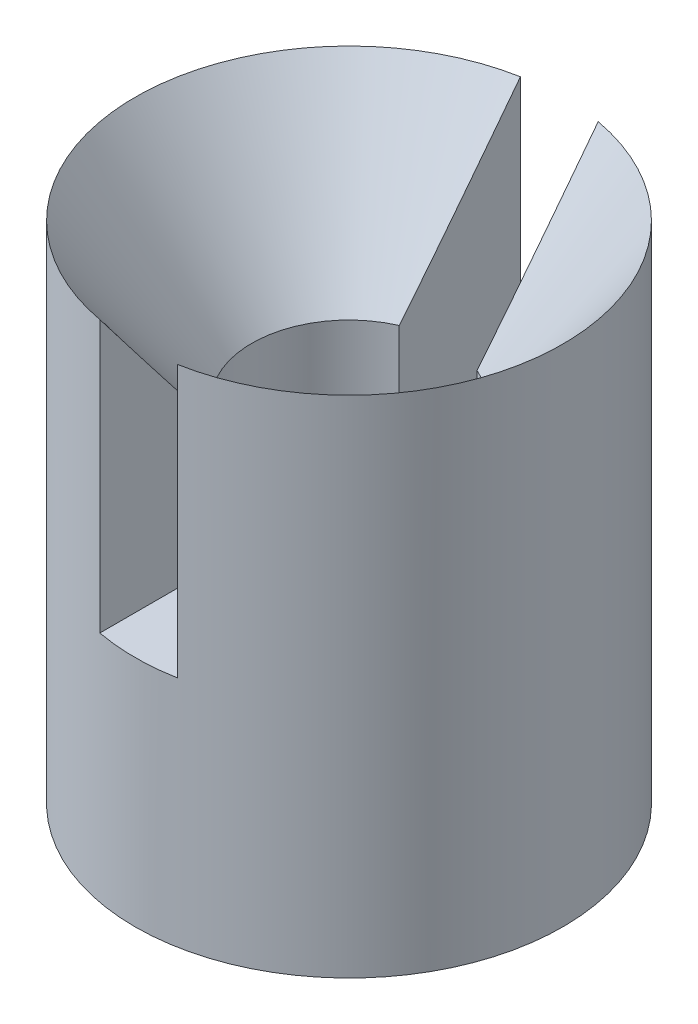
SolidWorks part; units mm, degrees
material "PBT General Purpose"
ref_plane "Front" through (0, 0, 0) normal (0, 0, 1) x (1, 0, 0)
ref_plane "Top" through (0, 0, 0) normal (0, 1, 0) x (1, 0, 0)
ref_plane "Right" through (0, 0, 0) normal (1, 0, 0) x (0, 0, -1)
sketch "Sketch1" plane through (0, 0, 0) normal (0, 1, 0) x (1, 0, 0)
  circle A0 centre (0, 0) radius 5.5
  dimension "D1" = 11
extrude "Boss-Extrude1" add sketch "Sketch1" along normal blind 13
sketch "Sketch2" plane through (0, 0, 0) normal (0, -1, 0) x (1, 0, 0)
  circle A0 centre (0, 0) radius 2.5
extrude "Cut-Extrude1" cut sketch "Sketch2" against normal through all
chamfer "Chamfer1" distance 4 angle 37 1 edges at (0, 13, -2.5) first distance on face at (0, 13, -2.5)
ref_plane "Plane1" through (0, 13, 0) normal (0, 1, 0) x (1, 0, 0)
sketch "Sketch4" plane through (0, 13, 0) normal (0, 1, 0) x (1, 0, 0)
  line L1 (-1, -6) -> (1, -6)
  line L2 (-1, -6) -> (-1, 6)
  line L3 (-1, 6) -> (1, 6)
  line L4 (1, -6) -> (1, 6)
  line L5 (-1, -6) -> (1, 6) construction
  line L6 (-1, 6) -> (1, -6) construction
  point P0 (0, 0)
  dimension "D1" = 2
  dimension "D2" = 12
extrude "Cut-Extrude2" cut sketch "Sketch4" against normal blind 7
sketch "Sketch5" plane through (0, 0, 0) normal (1, 0, 0) x (0, 0, -1)
  circle A0 centre (0, 3) radius 1
  dimension "D1" = 3
  dimension "D2" = 2
extrude "Cut-Extrude3" cut sketch "Sketch5" against normal blind 7
cosmetic thread "Cosmetic Thread1" parameters "D2"=3
